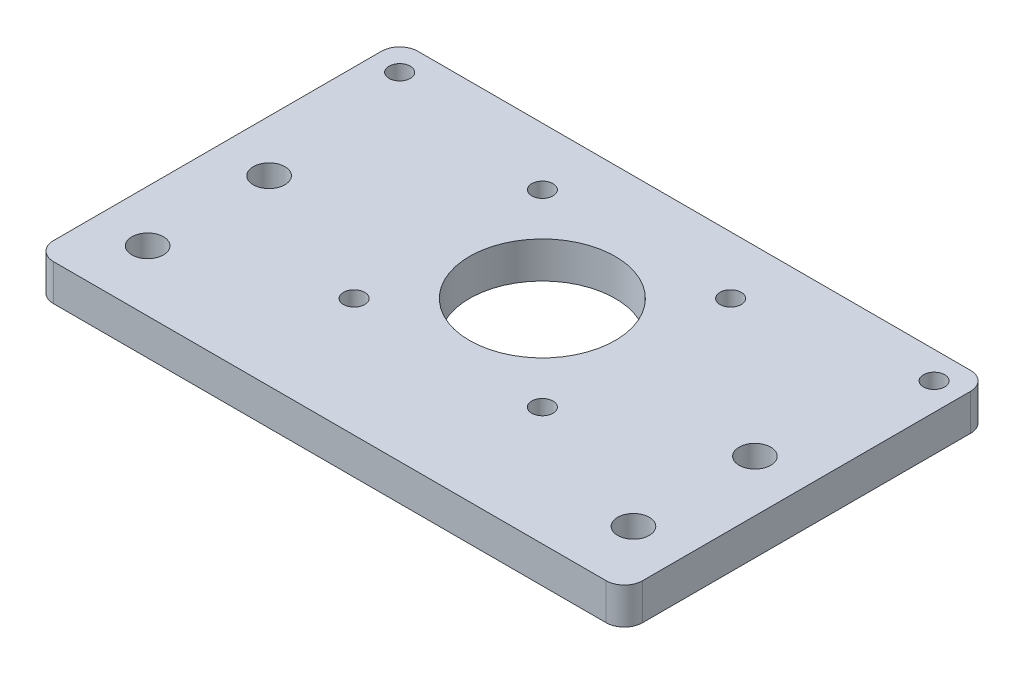
SolidWorks part; units mm, degrees
material "Polycarbonate (PC)"
ref_plane "Front Plane" through (0, 0, 0) normal (0, 0, 1) x (1, 0, 0)
ref_plane "Top Plane" through (0, 0, 0) normal (0, 1, 0) x (1, 0, 0)
ref_plane "Right Plane" through (0, 0, 0) normal (1, 0, 0) x (0, 0, -1)
sketch "Sketch1" plane through (0, 0, 0) normal (0, 1, 0) x (1, 0, 0)
  line L1 (48.5, -30) -> (-48.5, -30)
  line L2 (48.5, -30) -> (48.5, 30)
  line L3 (48.5, 30) -> (-48.5, 30)
  line L4 (-48.5, -30) -> (-48.5, 30)
  line L5 (48.5, -30) -> (-48.5, 30) construction
  line L6 (48.5, 30) -> (-48.5, -30) construction
  point P0 (0, 0)
  dimension "D1" = 97
  dimension "D2" = 60
extrude "Base" add sketch "Sketch1" along normal blind 6
sketch "Sketch2" plane through (0, 6, 0) normal (0, 1, 0) x (1, 0, 0)
  line L1 (0, 5) -> (0, 17.5) construction
  line L2 (-48.5, -30) -> (48.5, -30) construction
  circle A2 centre (0, 5) radius 12
  dimension "D1" = 24
  dimension "D2" = 35
extrude "StepperCaseHole" cut sketch "Sketch2" against normal through all
fillet "FilletEdges3mm" radius 3 4 edges at (48.5, 3, 30) (48.5, 3, -30) (-48.5, 3, -30) (-48.5, 3, 30)
hole_wizard "Ø3.5mm CableTieHoles" positions "Sketch6" profile "Sketch7" hole size "Ø3.5" standard "ISO" end condition through all
sketch "Sketch6" plane through (0, 0, 0) normal (0, -1, 0) x (-1, 0, 0)
  line L0 (-45.5, 30) -> (45.5, 30) construction
  line L1 (-48.5, -27) -> (-48.5, 27) construction
  line L2 (48.5, 27) -> (48.5, -27) construction
  point P0 (-44, 25.5)
  point P2 (44, 25.5)
  dimension "D1" = 4.5
  dimension "D2" = 4.5
  dimension "D3" = 4.5
sketch "Sketch7" plane through (44, 0, -25.5) normal (1, 0, 0) x (0, 0, -1)
  line L0 (0, 0) -> (0, 6)
  line L1 (0, 6) -> (1.75, 6)
  line L2 (1.75, 6) -> (1.75, 0)
  line L5 (1.75, 0) -> (0, 0)
  line L11 (0, -6.35) -> (0, 107.95) construction
  dimension "Thru Hole Dia." = 3.5
  dimension "Thru Hole Depth" = 6
hole_wizard "Ø5.2 (5.2) HolesForCorners" positions "Sketch8" profile "Sketch9" hole size "Ø5.2" standard "ISO" end condition through all
sketch "Sketch8" plane through (0, 6, 0) normal (0, 1, 0) x (1, 0, 0)
  line L0 (0, 0) -> (0, 10.0505) construction
  line L2 (-45.5, -30) -> (45.5, -30) construction
  point P0 (-40, 0)
  point P2 (-40, -20)
  point P4 (40, 0)
  point P6 (40, -20)
  dimension "D1" = 80
  dimension "D2" = 20
  dimension "D3" = 10
sketch "Sketch9" plane through (-40, 6, 0) normal (1, 0, 0) x (0, 0, 1)
  line L0 (0, 0) -> (0, 6)
  line L1 (0, 6) -> (2.6, 6)
  line L2 (2.6, 6) -> (2.6, 0)
  line L5 (2.6, 0) -> (0, 0)
  line L11 (0, -6.35) -> (0, 107.95) construction
  dimension "Thru Hole Dia." = 5.2
  dimension "Thru Hole Depth" = 6
hole_wizard "Ø3.5 (3.5) StepperMountHoles" positions "Sketch10" profile "Sketch11" hole size "Ø3.5" standard "ISO" end condition through all
sketch "Sketch10" plane through (0, 6, 0) normal (0, 1, 0) x (1, 0, 0)
  line L0 (0, 5) -> (-9.0309, 5) construction
  line L2 (0, 12.5358) -> (0, 5) construction
  point P0 (-15.5, 20.5)
  point P2 (-15.5, -10.5)
  point P4 (15.5, -10.5)
  point P6 (15.5, 20.5)
  dimension "D1" = 31
  dimension "D2" = 31
sketch "Sketch11" plane through (-15.5, 6, -20.5) normal (1, 0, 0) x (0, 0, 1)
  line L0 (0, 0) -> (0, 6)
  line L1 (0, 6) -> (1.75, 6)
  line L2 (1.75, 6) -> (1.75, 0)
  line L5 (1.75, 0) -> (0, 0)
  line L11 (0, -6.35) -> (0, 107.95) construction
  dimension "Thru Hole Dia." = 3.5
  dimension "Thru Hole Depth" = 6
